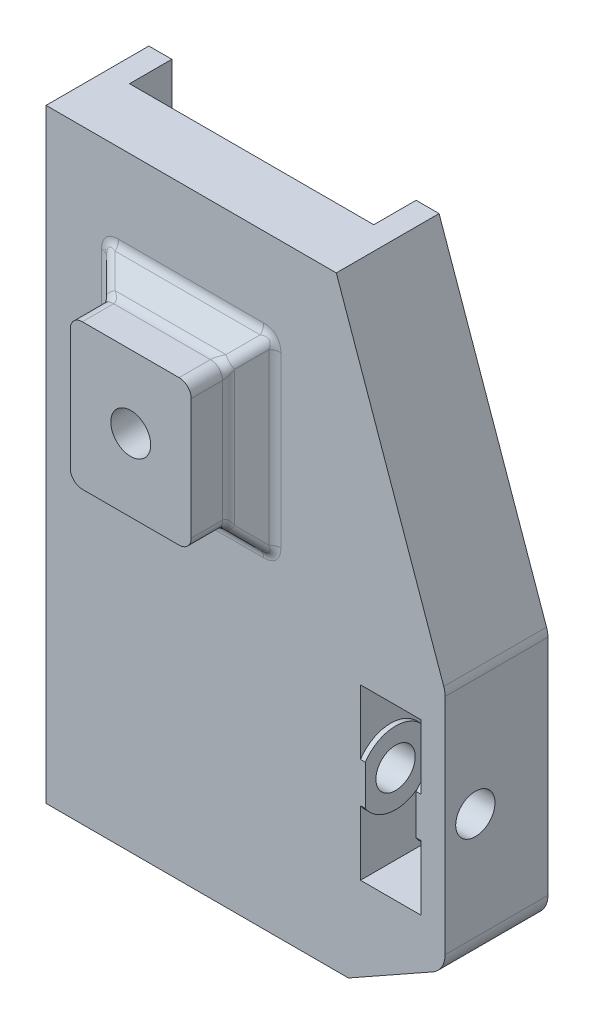
SolidWorks part; units mm, degrees
material "ABS"
ref_plane "前视基准面" through (0, 0, 0) normal (0, 0, 1) x (1, 0, 0)
ref_plane "上视基准面" through (0, 0, 0) normal (0, 1, 0) x (1, 0, 0)
ref_plane "右视基准面" through (0, 0, 0) normal (1, 0, 0) x (0, 0, -1)
other "Configuration Table"
sketch "草图1" plane through (0, 0, 0) normal (0, 0, 1) x (1, 0, 0)
  line L0 (33, 24.5) -> (24, 50)
  line L1 (24, 50) -> (0, 50)
  line L2 (0, 50) -> (0, 0)
  line L5 (33, 4.5) -> (33, 24.5)
  line L6 (26, 7.5) -> (31, 7.5)
  line L7 (26, 21.5) -> (26, 7.5)
  line L12 (31, 21.5) -> (26, 21.5)
  line L17 (31, 7.5) -> (31, 21.5)
  line L18 (0, 0) -> (25, 0)
  line L20 (25, 0) -> (33, 4.5)
  line L24 (0, 0) -> (25, 0)
  line L25 (33, 4.5) -> (33, 24.5)
  line L26 (33, 24.5) -> (24, 50)
  circle A0 centre (12, 35) radius 1.65
  dimension "D5" = 3.3
  dimension "D6" = 12
  dimension "D7" = 15
  dimension "D2" = 50
  dimension "D3" = 90
  dimension "D4" = 4.5
  dimension "D8" = 28.5
  dimension "D9" = 26
  dimension "D10" = 5
  dimension "D11" = 14
  dimension "D12" = 25
  dimension "D13" = 33
  dimension "D15" = 20
  dimension "D16" = 24
  dimension "D17" = 5
extrude "凸台-拉伸1" add sketch "草图1" against normal blind 8.5 contours L18 L20 L5 L0 L1 L2 A0 L17 L6 L7 L12 region at (14.6931, 24.4294, 0)
sketch "草图2" plane through (0, 50, 0) normal (0, 1, 0) x (1, 0, 0)
  line L0 (24, 8.5) -> (0, 8.5) construction
  line L1 (1.9, 8.5) -> (22.1, 8.5)
  line L2 (1.9, 8.5) -> (1.9, 5)
  line L3 (1.9, 5) -> (22.1, 5)
  line L4 (22.1, 8.5) -> (22.1, 5)
  line L5 (0, 8.5) -> (0, 0) construction
  dimension "D1" = 1.9
  dimension "D2" = 20.2
  dimension "D3" = 3.5
extrude "切除-拉伸1" cut sketch "草图2" against normal through all
sketch "草图3" plane through (33, 0, 0) normal (1, 0, 0) x (0, 0, -1)
  line L0 (0, 4.5) -> (0, 24.5) construction
  circle A0 centre (2.5, 14.5) radius 1.625
  dimension "D1" = 3.25
  dimension "D2" = 2.5
  dimension "D3" = 7
extrude "切除-拉伸2" cut sketch "草图3" against normal up to surface (7 mm away) up to face at (26, 14.5, -4.25)
sketch "草图4" plane through (26, 0, 0) normal (1, 0, 0) x (0, 0, -1)
  circle A0 centre (2.5, 14.5) radius 1
  dimension "D1" = 2
extrude "切除-拉伸3" cut sketch "草图4" against normal up to surface (3.9 mm away) up to face at (22.1, 25, -6.75)
sketch "草图5" plane through (26, 0, 0) normal (1, 0, 0) x (0, 0, -1)
  line L0 (0, 21.5) -> (0, 7.5) construction
  line L1 (0, 16.1583) -> (0, 12.8417)
  arc A0 (0, 12.8417) -> (0, 16.1583) centre (2.5, 14.5) ccw
  circle A2 centre (2.5, 14.5) radius 1 construction
  circle A3 centre (2.5, 14.5) radius 1
  dimension "D1" = 6
extrude "凸台-拉伸2" add sketch "草图5" along normal blind 0.4
sketch "草图6" plane through (31, 0, 0) normal (-1, 0, 0) x (0, 0, 1)
  line L0 (0, 7.5) -> (0, 21.5) construction
  line L1 (0, 12.8417) -> (0, 16.1583)
  circle A0 centre (-2.5, 14.5) radius 1.625 construction
  circle A1 centre (-2.5, 14.5) radius 1.625
  arc A2 (0, 16.1583) -> (0, 12.8417) centre (-2.5, 14.5) ccw
  dimension "D1" = 6
extrude "凸台-拉伸3" add sketch "草图6" along normal blind 0.4
fillet "圆角1" radius 2 2 edges at (33, 4.5, -4.25) (33, 24.5, -4.25)
sketch "草图7" plane through (33, 0, 0) normal (1, 0, 0) x (0, 0, -1)
  circle A0 centre (2.5, 14.5) radius 1.625 construction
  circle A1 centre (2.5, 14.5) radius 1.625
extrude "切除-拉伸4" cut sketch "草图7" against normal through all
sketch "草图8" plane through (0, 0, -8.5) normal (0, 0, -1) x (-1, 0, 0)
  line L0 (-26, 21.5) -> (-26, 7.5) construction
  line L1 (-31, 7.5) -> (-26, 7.5)
  line L2 (-31, 7.5) -> (-31, -0.36)
  line L3 (-31, -0.36) -> (-26, -0.36)
  line L4 (-26, 7.5) -> (-26, -0.36)
extrude "切除-拉伸5" cut sketch "草图8" against normal blind 2
fillet "圆角2" radius 0.5 2 edges at (26, 0.5625, -7.5) (31, 3.375, -7.5)
fillet "圆角3" radius 1 4 edges at (31.2476, 3.7983, -6.5) (25.9316, 0.6025, -6.5) (31, 5.865, -6.5) (26, 4.1775, -6.5)
sketch "草图9" plane through (0, 0, 0) normal (0, 0, 1) x (1, 0, 0)
  line L1 (17, 29) -> (7, 29)
  line L2 (17, 29) -> (17, 41)
  line L3 (17, 41) -> (7, 41)
  line L4 (7, 29) -> (7, 41)
  line L5 (17, 29) -> (7, 41) construction
  line L6 (17, 41) -> (7, 29) construction
  circle A0 centre (12, 35) radius 1.65 construction
  circle A1 centre (12, 35) radius 1.65
  dimension "D1" = 10
  dimension "D2" = 12
extrude "凸台-拉伸4" add sketch "草图9" along normal blind 5
chamfer "倒角1" distance 2 angle 45 4 edges at (12, 29, 0) (7, 35, 0) (12, 41, 0) (17, 35, 0)
fillet "圆角5" radius 1 16 edges at (12, 41, 2) (12, 43, 0) (7, 35, 2) (5, 35, 0) (6, 42, 1) (12, 29, 2) (12, 27, 0) (6, 28, 1) (19, 35, 0) (18, 28, 1) (17, 35, 2) (18, 42, 1) (17, 41, 3.5) (7, 41, 3.5) (7, 29, 3.5) (17, 29, 3.5)
